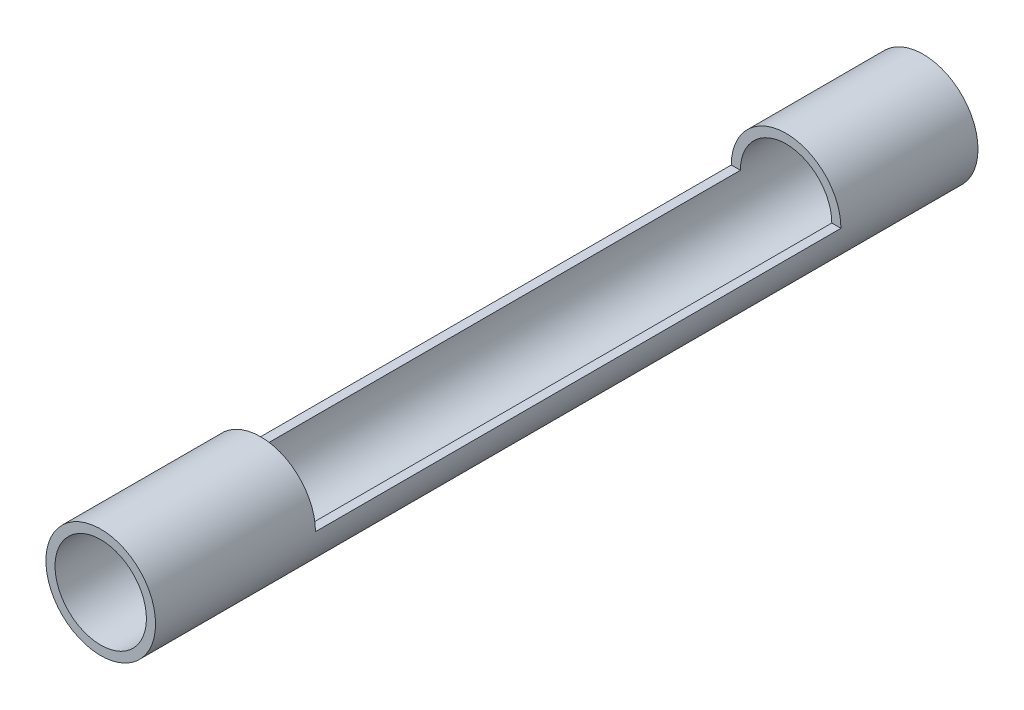
SolidWorks part; units mm, degrees
ref_plane "Piano frontale" through (0, 0, 0) normal (0, 0, 1) x (1, 0, 0)
ref_plane "Piano superiore" through (0, 0, 0) normal (0, 1, 0) x (1, 0, 0)
ref_plane "Piano destro" through (0, 0, 0) normal (1, 0, 0) x (0, 0, -1)
sketch "Schizzo1" plane through (0, 0, 0) normal (0, 0, 1) x (1, 0, 0)
  circle A0 centre (0, 0) radius 12
  circle A1 centre (0, 0) radius 10
  dimension "D1" = 24
  dimension "D2" = 20
extrude "Estrusione-Estrusione1" add sketch "Schizzo1" along normal blind 180
cosmetic thread "Filettatura cosmetica2" parameters "D1"=15, "D2"=22
cosmetic thread "Filettatura cosmetica3" parameters "D1"=15, "D2"=22
cosmetic thread "Filettatura cosmetica4" parameters "D1"=15, "D2"=14
cosmetic thread "Filettatura cosmetica5" parameters "D1"=15, "D2"=14
sketch "Schizzo2" plane through (0, 0, 0) normal (1, 0, 0) x (0, 0, -1)
  line L0 (0, 12) -> (-180, 12) construction
  line L1 (-145, 12) -> (-30, 12)
  line L2 (-145, 12) -> (-145, 0)
  line L3 (-145, 0) -> (-30, 0)
  line L4 (-30, 12) -> (-30, 0)
  line L5 (-180, 12) -> (-180, -12) construction
  line L6 (0, -12) -> (0, 12) construction
  line L7 (-157.0473, 0) -> (6.4474, 0) construction
  dimension "D1" = 35
  dimension "D2" = 30
extrude "Taglio-Estrusione1" cut sketch "Schizzo2" against normal blind 20 and the other way blind 20
